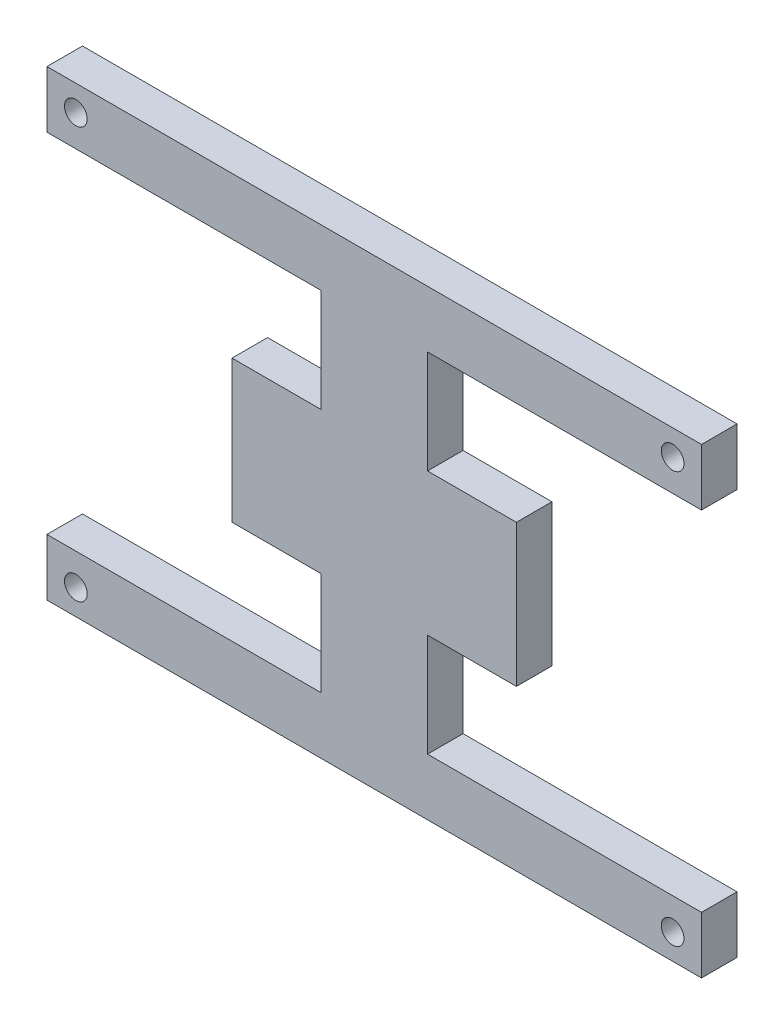
SolidWorks part; units mm, degrees
ref_plane "前视基准面" through (0, 0, 0) normal (0, 0, 1) x (1, 0, 0)
ref_plane "上视基准面" through (0, 0, 0) normal (0, 1, 0) x (1, 0, 0)
ref_plane "右视基准面" through (0, 0, 0) normal (1, 0, 0) x (0, 0, -1)
other "Configuration Table"
sketch "草图1" plane through (0, 0, 0) normal (0, 0, 1) x (1, 0, 0)
  line L0 (46.0375, -32.5) -> (46.0375, 32.5) construction
  line L1 (-46.0375, 32.5) -> (46.0375, 32.5)
  line L2 (-46.0375, 32.5) -> (-46.0375, 24.5)
  line L3 (-46.0375, 24.5) -> (46.0375, 24.5)
  line L4 (46.0375, 32.5) -> (46.0375, 24.5)
  line L5 (-46.0375, -32.5) -> (-46.0375, 32.5) construction
  line L6 (46.0375, -32.5) -> (-46.0375, -32.5)
  line L7 (46.0375, -32.5) -> (46.0375, -24.5)
  line L8 (46.0375, -24.5) -> (-46.0375, -24.5)
  line L9 (-46.0375, -32.5) -> (-46.0375, -24.5)
  line L10 (0, 24.5) -> (0, -24.5) construction
  line L15 (-7.5, 0) -> (7.5, 0) construction
  line L16 (-7.5, -24.5) -> (7.5, -24.5)
  line L17 (-7.5, -24.5) -> (-7.5, 24.5)
  line L18 (-7.5, 24.5) -> (7.5, 24.5)
  line L19 (7.5, -24.5) -> (7.5, 24.5)
  line L20 (-7.5, -24.5) -> (7.5, 24.5) construction
  line L21 (-7.5, 24.5) -> (7.5, -24.5) construction
  line L23 (-20, -10) -> (20, -10)
  line L24 (-20, -10) -> (-20, 10)
  line L25 (-20, 10) -> (20, 10)
  line L26 (20, -10) -> (20, 10)
  line L27 (-20, -10) -> (20, 10) construction
  line L28 (-20, 10) -> (20, -10) construction
  circle A0 centre (-41.9735, 28.92) radius 1.6
  circle A1 centre (41.9735, 28.92) radius 1.6
  circle A2 centre (41.9735, -28.92) radius 1.6
  circle A3 centre (-41.9735, -28.92) radius 1.6
  point P28 (0, 0)
  point P36 (0, 0)
  dimension "D3" = 3.2
  dimension "D4" = 3.2
  dimension "D5" = 3.2
  dimension "D6" = 3.2
  dimension "D1" = 8
  dimension "D2" = 8
  dimension "D7" = 15
  dimension "D8" = 20
  dimension "D9" = 40
extrude "凸台-拉伸1" add sketch "草图1" along normal blind 5 contours L4 L1 L2 L3 A1 A0 | L23 L26 L25 L19 | L25 L17 L23 L19 | L25 L24 L23 L17 | L17 L25 L19 L3 | L9 L6 L7 L8 A3 A2 | L23 L17 L8 L19 region at (0, 28.4906, 0) region at (0, 17.25, 0) region at (0, 0, 0) region at (-13.75, 0, 0) region at (13.75, 0, 0) region at (0, -17.25, 0) region at (0, -28.4906, 0)
